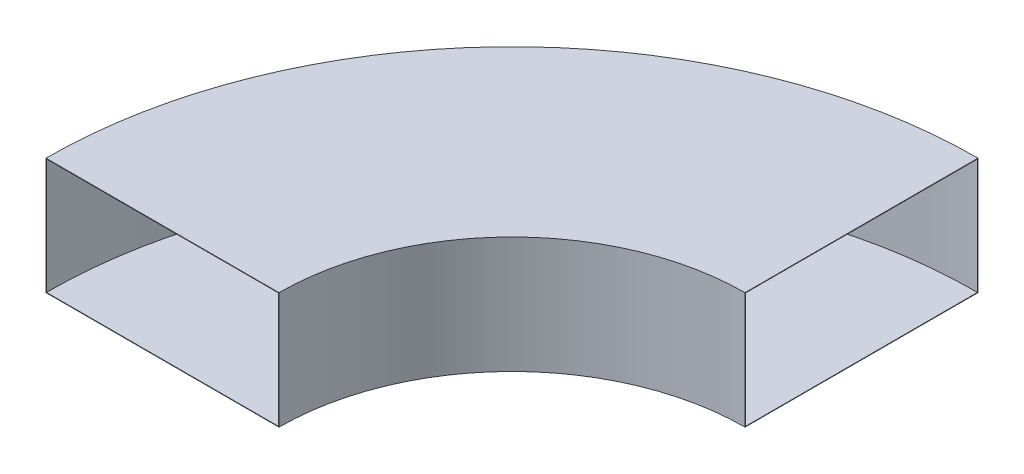
SolidWorks part; units mm, degrees
note: '?' marks a value the reader was unsure of.
material "Plain Carbon Steel"
ref_plane "Front Plane" through (0, 0, 0) normal (0, 0, 1) x (1, 0, 0)
ref_plane "Top Plane" through (0, 0, 0) normal (0, 1, 0) x (1, 0, 0)
ref_plane "Right Plane" through (0, 0, 0) normal (1, 0, 0) x (0, 0, -1)
sketch "ElbowArc" plane through (0, 0, 0) normal (0, 1, 0) x (1, 0, 0)
  arc A0 (0, 1500) -> (-1500, 0) centre (0, 0) ccw
  dimension "BendRadius" = 1500
  dimension "BendAngle" = 90
sketch "Sketch1" plane through (0, 0, 0) normal (1, 0, 0) x (0, 0, -1)
  line L0 (2000, 0) -> (1000, 0) construction
  line L1 (1000, 250) -> (2000, 250)
  line L2 (1000, 250) -> (1000, -250)
  line L3 (1000, -250) -> (2000, -250)
  line L4 (2000, 250) -> (2000, -250)
  line L6 (1500, 0) -> (4772.2061, 0) construction
  dimension "Height" = 500
  dimension "Width" = 1000
  dimension "AlignmentAngle" = 0
sweep "Sweep-Thin1" add profiles "Sketch1" path "ElbowArc" parameters "Thickness"=2
sketch "Sketch2" plane through (0, 0, 0) normal (0, 1, 0) x (1, 0, 0)
  point P0 (0, 1500)
  point P1 (-1500, 0)
other "CPoint1" parameters "Diameter"=564.1896, "StubLength"=500
ref_axis "Axis1" through (10, 0, -1500) along (-1, 0, 0)?
other "CPoint2" parameters "Diameter"=564.1896, "StubLength"=500
ref_axis "Axis2" through (-1500, 0, 10) along (0, 0, -1)?
